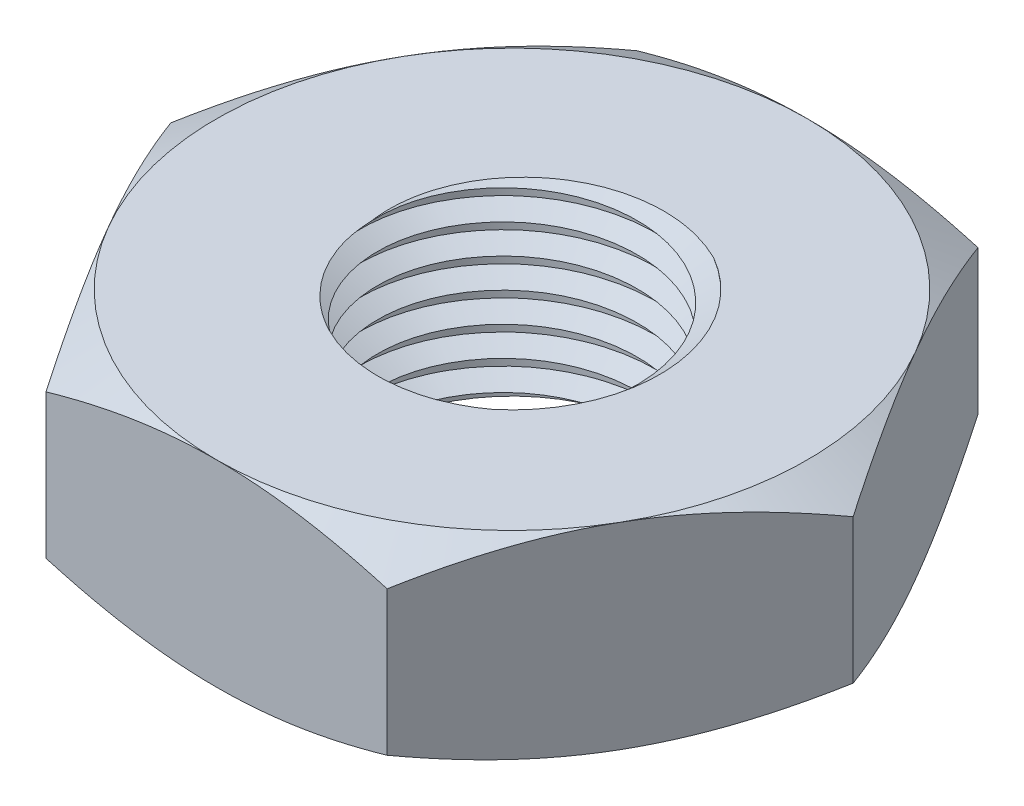
SolidWorks part; units mm, degrees
ref_plane "Front Plane" through (0, 0, 0) normal (0, 0, 1) x (1, 0, 0)
ref_plane "Top Plane" through (0, 0, 0) normal (0, 1, 0) x (1, 0, 0)
ref_plane "Right Plane" through (0, 0, 0) normal (1, 0, 0) x (0, 0, -1)
sketch "Sketch1" plane through (0, 0, 0) normal (0, 1, 0) x (1, 0, 0)
  line L1 (17.3205, 0) -> (8.6603, 15)
  line L2 (8.6603, 15) -> (-8.6603, 15)
  line L3 (-8.6603, 15) -> (-17.3205, 0)
  line L4 (-17.3205, 0) -> (-8.6603, -15)
  line L5 (-8.6603, -15) -> (8.6603, -15)
  line L6 (8.6603, -15) -> (17.3205, 0)
  circle A0 centre (0, 0) radius 15 construction
extrude "Boss-Extrude1" add sketch "Sketch1" along normal blind 10
sketch "Sketch2" plane through (0, 0, 0) normal (0, -1, 0) x (1, 0, 0)
  circle A0 centre (0, 0) radius 15
extrude "Cut-Extrude2" cut sketch "Sketch2" against normal blind 10 draft 60 flip side to cut
ref_plane "Plane1" through (0, 5, 0) normal (0, -1, 0) x (-1, 0, 0)
mirror "Mirror1" about plane through (0, 5, 0) normal (0, -1, 0) of "Cut-Extrude2"
sketch "Sketch4" plane through (0, 5, 0) normal (0, -1, 0) x (-1, 0, 0)
  circle A0 centre (0, 0) radius 7.5
extrude "Cut-Extrude3" cut sketch "Sketch4" against normal through all both and the other way through all
ref_plane "Plane2" through (0, 12, 0) normal (0, 1, 0) x (1, 0, 0)
sketch "Sketch6" plane through (0, 12, 0) normal (0, 1, 0) x (1, 0, 0)
  circle A0 centre (0, 0) radius 7.5
sketch "Sketch8" plane through (0, 0, 0) normal (0, 0, 1) x (1, 0, 0)
  line L0 (-7.5, 12) -> (-7.5, 10.9585)
  line L1 (7.5, 12) -> (-7.5, 12) construction
  line L2 (16.5, 12) -> (-16.5, 12) construction
  line L3 (-7.5, 10.9585) -> (-6.598, 11.4792)
  line L4 (-6.598, 11.4792) -> (-7.5, 12)
curve "Helix/Spiral1" pitch 1.5 height 15 radius 7.5 centre (0, 12, 0) axis (0, -1, 0) start towards (0, 0, 1)
sweep "Sweep1" add profiles "Sketch8" path "Helix/Spiral1"
sketch "Sketch9" plane through (0, 10, 0) normal (0, 1, 0) x (1, 0, 0)
  line L1 (-13.1581, -12.7045) -> (13.1581, -12.7045)
  line L2 (-13.1581, -12.7045) -> (-13.1581, 12.7045)
  line L3 (-13.1581, 12.7045) -> (13.1581, 12.7045)
  line L4 (13.1581, -12.7045) -> (13.1581, 12.7045)
  line L5 (-13.1581, -12.7045) -> (13.1581, 12.7045) construction
  line L6 (-13.1581, 12.7045) -> (13.1581, -12.7045) construction
  point P0 (0, 0)
extrude "Cut-Extrude4" cut sketch "Sketch9" along normal through all
mirror "Mirror2" about plane through (0, 5, 0) normal (0, -1, 0) of "Cut-Extrude4"
